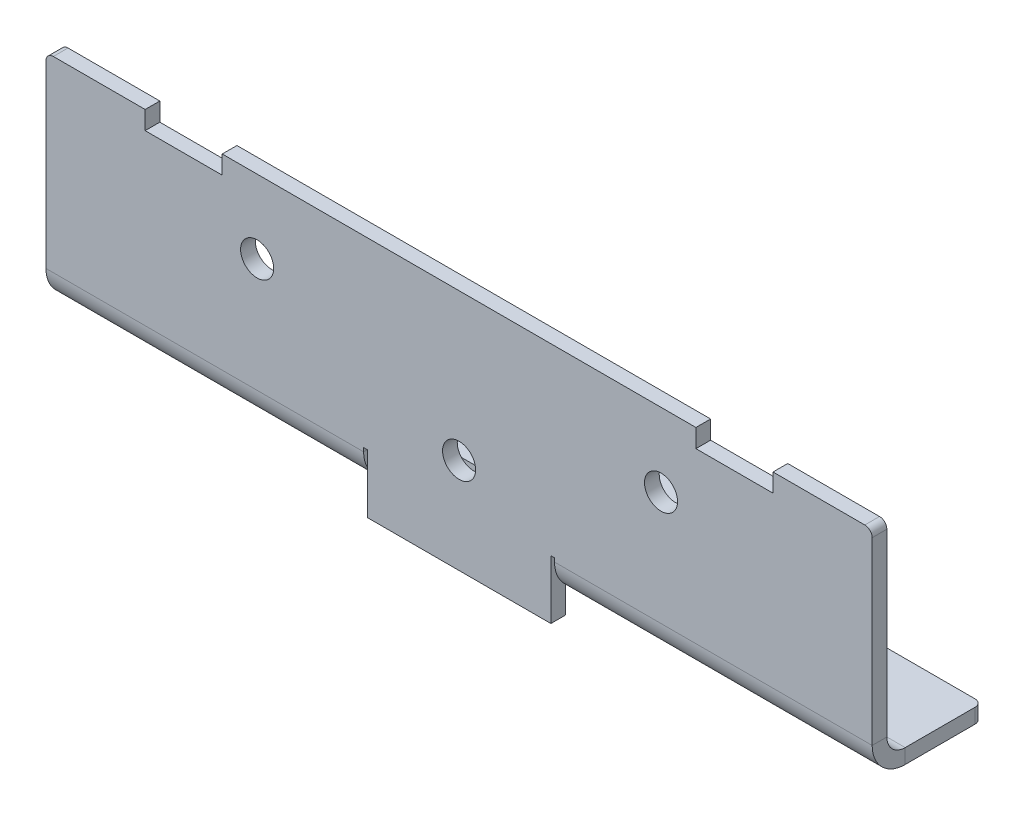
SolidWorks part; units mm, degrees
note: The reader was unsure of these and kept them because the rebuilt part matched: thickness of "Базовая кромка1", "Ребро-кромка1", "Листовой металл6", "Листовой металл7", "Листовой металл9", "Листовой металл10", "Листовой металл11", "Листовой металл12", "Листовой металл13", "Листовой металл14"; flange length of "Ребро-кромка1".
material "1.7033 (34Cr4)"
ref_plane "Спереди" through (0, 0, 0) normal (0, 0, 1) x (1, 0, 0)
ref_plane "Сверху" through (0, 0, 0) normal (0, 1, 0) x (1, 0, 0)
ref_plane "Справа" through (0, 0, 0) normal (1, 0, 0) x (0, 0, -1)
sketch "Эскиз6" plane through (0, 0, 0) normal (0, 0, 1) x (1, 0, 0)
  line L1 (112.5, -30) -> (-112.5, -30)
  line L2 (112.5, -30) -> (112.5, 30)
  line L3 (112.5, 30) -> (-112.5, 30)
  line L4 (-112.5, -30) -> (-112.5, 30)
  line L5 (112.5, -30) -> (-112.5, 30) construction
  line L6 (112.5, 30) -> (-112.5, -30) construction
  point P0 (0, 0)
  dimension "D1" = 225
  dimension "D2" = 60
base flange "Базовая кромка1" sketch "Эскиз6" thickness 4 reverse thickness direction no parameters "D1"=0.7366
edge flange "Ребро-кромка1" sketch "Эскиз13" flange angle 90 flange length 45 flange position material inside bend radius 5 thickness 4 relief rectangular parameters "D6"=10
sketch "Эскиз13" plane through (0, -30, -4) normal (0, 1, 0) x (1, 0, 0)
  line L2 (-112.5, 0) -> (-112.5, 41)
  line L3 (-112.5, 41) -> (112.5, 41)
  line L4 (112.5, 41) -> (112.5, 0)
  line L5 (112.5, 0) -> (-112.5, 0) construction
  line L6 (112.5, 0) -> (-112.5, 0)
bend "EdgeBend1" bend radius 5 bend angle 90 parameters "D5"=1
sketch "Эскиз15" plane through (0, -30, 0) normal (0, -1, 0) x (1, 0, 0)
  line L0 (-112.5, -45) -> (-112.5, -30)
  line L1 (-112.5, -45) -> (-112.5, -9) construction
  line L2 (-112.5, -30) -> (-30, -30)
  line L3 (-30, -30) -> (-15, -45)
  line L4 (112.5, -45) -> (-112.5, -45) construction
  line L5 (-15, -45) -> (-112.5, -45)
  line L6 (0, 0) -> (0, -50000) construction
  line L7 (-112.5, 0) -> (112.5, 0) construction
  line L8 (15, -45) -> (112.5, -45)
  line L9 (30, -30) -> (15, -45)
  line L10 (112.5, -30) -> (30, -30)
  line L11 (112.5, -45) -> (112.5, -30)
  point P13 (0, 0)
  dimension "D1" = 30
  dimension "D2" = 90
  dimension "D3" = 15
extrude "Вырез-Вытянуть2" cut sketch "Эскиз15" against normal blind 5 normal cut yes
sketch "Эскиз20" plane through (0, -30, 0) normal (0, -1, 0) x (-1, 0, 0)
  line L0 (0, 0) -> (0, 50000) construction
  line L1 (-112.5, 30) -> (-30, 30) construction
  point P0 (-75, 20)
  point P3 (75, 20)
  point P6 (0, 35)
  dimension "D1" = 10
  dimension "D2" = 15
  dimension "D3" = 150
hole_wizard "Отверстие с зазором M81" positions "Эскиз20" profile "Эскиз17" hole size "M8" standard "ISO" end condition up to next
sketch "Эскиз17" plane through (75, -30, -20) normal (1, 0, 0) x (0, 0, -1)
  line L0 (0, 0) -> (0, 4)
  line L1 (0, 4) -> (4.5, 4)
  line L2 (4.5, 4) -> (4.5, 0)
  line L5 (4.5, 0) -> (0, 0)
  line L11 (0, -6.35) -> (0, 107.95) construction
  dimension "Диаметр сквозного отверстия" = 9
  dimension "Глубина сквозного отверстия" = 4
sketch "Эскиз21" plane through (0, -30, 0) normal (0, -1, 0) x (1, 0, 0)
  line L0 (-112.5, 0) -> (112.5, 0) construction
  line L1 (-26, 0) -> (26, 0)
  line L2 (-26, 0) -> (-26, -17)
  line L3 (-26, -17) -> (26, -17)
  line L4 (26, 0) -> (26, -17)
  line L6 (0, 0) -> (0, -50000) construction
  dimension "D1" = 52
  dimension "D2" = 17
extrude "Вырез-Вытянуть3" cut sketch "Эскиз21" against normal blind 10 normal cut yes
sketch "Эскиз22" plane through (0, 0, 0) normal (0, 0, 1) x (1, 0, 0)
  line L0 (26, -20) -> (-26, -20) construction
  line L1 (-25, -20) -> (25, -20)
  line L2 (-25, -20) -> (-25, -36)
  line L3 (-25, -36) -> (25, -36)
  line L4 (25, -20) -> (25, -36)
  line L5 (0, 0) -> (0, -50000) construction
  dimension "D1" = 50
  dimension "D2" = 16
extrude "Бобышка-Вытянуть1" add sketch "Эскиз22" against normal blind 4
sketch "Эскиз23" plane through (0, 0, 0) normal (0, 0, 1) x (1, 0, 0)
  line L0 (112.5, 30) -> (-112.5, 30) construction
  line L1 (-85.5, 30) -> (-64.5, 30)
  line L2 (-85.5, 30) -> (-85.5, 25)
  line L3 (-85.5, 25) -> (-64.5, 25)
  line L4 (-64.5, 30) -> (-64.5, 25)
  line L5 (0, -1.111) -> (0, 49998.889) construction
  line L6 (-75, 30) -> (-75, 5.9728) construction
  line L9 (64.5, 30) -> (64.5, 25)
  line L10 (85.5, 30) -> (85.5, 25)
  line L12 (85.5, 25) -> (64.5, 25)
  line L14 (85.5, 30) -> (64.5, 30)
  line L15 (75, 30) -> (75, 9.2786) construction
  dimension "D1" = 21
  dimension "D2" = 5
  dimension "D3" = 150
extrude "Вырез-Вытянуть4" cut sketch "Эскиз23" against normal blind 10 normal cut yes
sketch "Эскиз26" plane through (0, 0, -4) normal (0, 0, -1) x (-1, 0, 0)
  line L0 (-64.5, 30) -> (64.5, 30) construction
  line L1 (0, 0) -> (0, -49.4291) construction
  circle A0 centre (-55, 10) radius 4.5
  circle A2 centre (55, 10) radius 4.5
  circle A3 centre (0, -10) radius 4.5
  dimension "D2" = 9
  dimension "D1" = 40
  dimension "D3" = 110
extrude "Вырез-Вытянуть5" cut sketch "Эскиз26" against normal blind 15
fillet "Скругление1" radius 2 8 edges at (-112.5, 30, -2) (112.5, 30, -2) (30, -28, -30) (15, -28, -45) (-15, -28, -45) (-30, -28, -30) (-112.5, -28, -30) (112.5, -28, -30)
sketch "Сгиб-Линии3" plane through (0, 0, 0) normal (0, 1, 0) x (1, 0, 0)
sketch "Граничная рамка3" plane through (0, 0, 0) normal (0, 1, 0) x (1, 0, 0)
sheet metal parameters "Листовой металл6" thickness 4 parameters "D1"=0.7366, "D7"=5
flat pattern "Развертка6" [suppressed]
sketch "Сгиб-Линии4" plane through (0, 0, 0) normal (0, 1, 0) x (1, 0, 0)
sketch "Граничная рамка4" [suppressed] plane through (0, 0, 0) normal (0, 1, 0) x (1, 0, 0)
sheet metal parameters "Листовой металл7" thickness 4 parameters "D1"=0.7366, "D7"=5
flat pattern "Развертка6" [suppressed]
sketch "Сгиб-Линии4" plane through (0, 0, 0) normal (0, 1, 0) x (1, 0, 0)
sketch "Граничная рамка4" [suppressed] plane through (0, 0, 0) normal (0, 1, 0) x (1, 0, 0)
bend of the flat pattern "Плоское состояние-<EdgeBend1>1"
sheet metal parameters "Листовой металл9" thickness 4 parameters "D1"=0.7366, "D7"=5
flat pattern "Развертка6" [suppressed]
sketch "Сгиб-Линии4" plane through (0, 0, 0) normal (0, 1, 0) x (1, 0, 0)
sketch "Граничная рамка4" [suppressed] plane through (0, 0, 0) normal (0, 1, 0) x (1, 0, 0)
bend of the flat pattern "Плоское состояние-<EdgeBend1>1"
sheet metal parameters "Листовой металл10" thickness 4 parameters "D1"=0.7366, "D7"=5
flat pattern "Развертка6" [suppressed]
sketch "Сгиб-Линии4" plane through (0, 0, 0) normal (0, 1, 0) x (1, 0, 0)
sketch "Граничная рамка4" [suppressed] plane through (0, 0, 0) normal (0, 1, 0) x (1, 0, 0)
bend of the flat pattern "Плоское состояние-<EdgeBend1>1"
sheet metal parameters "Листовой металл11" thickness 4 parameters "D1"=0.7366, "D7"=5
flat pattern "Развертка6" [suppressed]
sketch "Сгиб-Линии4" plane through (0, 0, 0) normal (0, 1, 0) x (1, 0, 0)
sketch "Граничная рамка4" [suppressed] plane through (0, 0, 0) normal (0, 1, 0) x (1, 0, 0)
bend of the flat pattern "Плоское состояние-<EdgeBend1>1"
sheet metal parameters "Листовой металл12" thickness 4 parameters "D1"=0.7366, "D7"=5
flat pattern "Развертка6" [suppressed]
sketch "Сгиб-Линии4" plane through (0, 0, 0) normal (0, 1, 0) x (1, 0, 0)
sketch "Граничная рамка4" [suppressed] plane through (0, 0, 0) normal (0, 1, 0) x (1, 0, 0)
bend of the flat pattern "Плоское состояние-<EdgeBend1>1"
sheet metal parameters "Листовой металл13" thickness 4 parameters "D1"=0.7366, "D7"=5
flat pattern "Развертка6" [suppressed]
sketch "Сгиб-Линии4" plane through (0, 0, 0) normal (0, 1, 0) x (1, 0, 0)
sketch "Граничная рамка4" [suppressed] plane through (0, 0, 0) normal (0, 1, 0) x (1, 0, 0)
bend of the flat pattern "Плоское состояние-<EdgeBend1>1"
sheet metal parameters "Листовой металл14" thickness 4 parameters "D1"=0.7366, "D7"=5
flat pattern "Развертка6" [suppressed]
sketch "Сгиб-Линии4" plane through (0, 0, 0) normal (0, 1, 0) x (1, 0, 0)
sketch "Граничная рамка4" [suppressed] plane through (0, 0, 0) normal (0, 1, 0) x (1, 0, 0)
bend of the flat pattern "Плоское состояние-<EdgeBend1>1"
